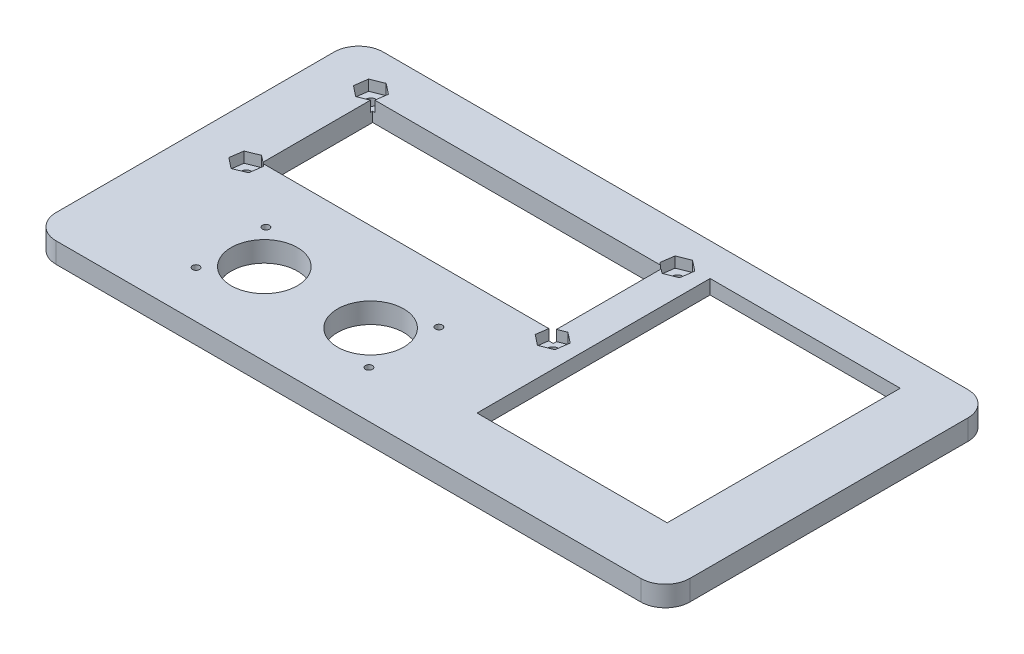
SolidWorks part; units mm, degrees
ref_plane "Front Plane" through (0, 0, 0) normal (0, 0, 1) x (1, 0, 0)
ref_plane "Top Plane" through (0, 0, 0) normal (0, 1, 0) x (1, 0, 0)
ref_plane "Right Plane" through (0, 0, 0) normal (1, 0, 0) x (0, 0, -1)
sketch "Sketch1" plane through (0, 0, 0) normal (0, 1, 0) x (1, 0, 0)
  line L1 (-77.5, -40) -> (77.5, -40)
  line L2 (-77.5, -40) -> (-77.5, 40)
  line L3 (-77.5, 40) -> (77.5, 40)
  line L4 (77.5, -40) -> (77.5, 40)
  line L5 (-77.5, -40) -> (77.5, 40) construction
  line L6 (-77.5, 40) -> (77.5, -40) construction
  point P0 (0, 0)
  dimension "D1" = 155
  dimension "D2" = 80
extrude "Boss-Extrude1" add sketch "Sketch1" along normal blind 5
sketch "Sketch2" plane through (0, 5, 0) normal (0, 1, 0) x (1, 0, 0)
  line L1 (-62.8518, 1.6691) -> (8.446, 1.6691)
  line L2 (-62.8518, 1.6691) -> (-62.8518, 28.7709)
  line L3 (-62.8518, 28.7709) -> (8.446, 28.7709)
  line L4 (8.446, 1.6691) -> (8.446, 28.7709)
  line L5 (-62.8518, 1.6691) -> (8.446, 28.7709) construction
  line L6 (-62.8518, 28.7709) -> (8.446, 1.6691) construction
  line L7 (-67.5, 15.22) -> (12.51, 15.22) construction
  line L8 (-67.5, 33) -> (12.51, 33) construction
  line L9 (-67.5, 33) -> (-67.5, -2.56) construction
  line L10 (-67.5, -2.56) -> (12.51, -2.56) construction
  line L11 (12.51, 33) -> (12.51, -2.56) construction
  line L12 (77.5, 40) -> (-77.5, 40) construction
  line L13 (-77.5, 40) -> (-77.5, -40) construction
  circle A0 centre (-64.96, -0.02) radius 1.27
  circle A1 centre (9.97, -0.02) radius 1.27
  circle A2 centre (9.97, 30.46) radius 1.27
  circle A3 centre (-64.96, 30.46) radius 1.27
  point P0 (-27.2029, 15.22)
  point P6 (-27.2029, 17.22)
  point P20 (-27.495, 15.22)
  dimension "D7" = 2.54
  dimension "D8" = 2.54
  dimension "D1" = 71.2978
  dimension "D2" = 27.1018
  dimension "D3" = 7
  dimension "D4" = 35.56
  dimension "D5" = 80.01
  dimension "D6" = 4.6482
  dimension "D9" = 33.02
  dimension "D10" = 77.47
  dimension "D11" = 5.08
  dimension "D12" = 10
extrude "Screen Cutout" cut sketch "Sketch2" against normal through all
sketch "Sketch8" plane through (0, 5, 0) normal (0, 1, 0) x (1, 0, 0)
  line L1 (-68.0135, 29.2327) -> (-65.4238, 27.202)
  line L2 (-65.4238, 27.202) -> (-62.3704, 28.4293)
  line L3 (-62.3704, 28.4293) -> (-61.9065, 31.6873)
  line L4 (-61.9065, 31.6873) -> (-64.4962, 33.718)
  line L5 (-64.4962, 33.718) -> (-67.5496, 32.4907)
  line L6 (-67.5496, 32.4907) -> (-68.0135, 29.2327)
  line L7 (6.9165, 29.2327) -> (9.5062, 27.202)
  line L8 (9.5062, 27.202) -> (12.5596, 28.4293)
  line L9 (12.5596, 28.4293) -> (13.0235, 31.6873)
  line L10 (13.0235, 31.6873) -> (10.4338, 33.718)
  line L11 (10.4338, 33.718) -> (7.3804, 32.4907)
  line L12 (7.3804, 32.4907) -> (6.9165, 29.2327)
  line L13 (6.9165, -1.2473) -> (9.5062, -3.278)
  line L14 (9.5062, -3.278) -> (12.5596, -2.0507)
  line L15 (12.5596, -2.0507) -> (13.0235, 1.2073)
  line L16 (13.0235, 1.2073) -> (10.4338, 3.238)
  line L17 (10.4338, 3.238) -> (7.3804, 2.0107)
  line L18 (7.3804, 2.0107) -> (6.9165, -1.2473)
  line L19 (-68.0135, -1.2473) -> (-65.4238, -3.278)
  line L20 (-65.4238, -3.278) -> (-62.3704, -2.0507)
  line L21 (-62.3704, -2.0507) -> (-61.9065, 1.2073)
  line L22 (-61.9065, 1.2073) -> (-64.4962, 3.238)
  line L23 (-64.4962, 3.238) -> (-67.5496, 2.0107)
  line L24 (-67.5496, 2.0107) -> (-68.0135, -1.2473)
  circle A0 centre (-64.96, 30.46) radius 2.85 construction
  circle A1 centre (9.97, 30.46) radius 2.85 construction
  circle A2 centre (9.97, -0.02) radius 2.85 construction
  circle A3 centre (-64.96, -0.02) radius 2.85 construction
  dimension "D1" = 5.7
extrude "Screen hex nuts" cut sketch "Sketch8" against normal blind 2.6
sketch "Sketch3" plane through (0, 5, 0) normal (0, 1, 0) x (1, 0, 0)
  line L0 (-40.5818, -20) -> (-14.5818, -20) construction
  line L1 (-48.7318, -11.45) -> (-48.7318, -28.55) construction
  line L2 (-48.7318, -28.55) -> (-6.4318, -28.55) construction
  line L3 (-62.4954, 1.6691) -> (7.3317, 1.6691) construction
  line L4 (-77.5, -40) -> (77.5, -40) construction
  line L7 (-27.5818, 26.9252) -> (-27.5818, -22.8987) construction
  circle A0 centre (-40.5818, -20) radius 8.1
  circle A1 centre (-14.5818, -20) radius 8.1
  circle A2 centre (-48.7318, -11.45) radius 0.85
  circle A3 centre (-6.4318, -11.45) radius 0.85
  circle A4 centre (-6.4318, -28.55) radius 0.85
  circle A5 centre (-48.7318, -28.55) radius 0.85
  point P4 (-27.5818, -28.55)
  point P14 (-27.5818, -20)
  point P19 (-27.5818, 1.6691)
  dimension "D1" = 16.2
  dimension "D2" = 26
  dimension "D3" = 1.7
  dimension "D4" = 17.1
  dimension "D5" = 20
  dimension "D6" = 42.3
  dimension "D7" = 8.55
extrude "Ultrasound Cutouts" cut sketch "Sketch3" against normal through all
sketch "Sketch4" plane through (0, 5, 0) normal (0, 1, 0) x (1, 0, 0)
  circle A0 centre (-21.6513, -28.8183) radius 0.85
  circle A1 centre (20.3487, -11.8183) radius 0.85
  circle A2 centre (-21.6513, -11.8183) radius 0.85
  circle A3 centre (20.3487, -28.8183) radius 0.85
  dimension "D1" = 1.7
  dimension "D2" = 17
  dimension "D3" = 42
extrude "Ultrasound Bolt Holes" [suppressed] cut sketch "Sketch4" against normal through all
sketch "Sketch5" plane through (0, 0, 0) normal (0, -1, 0) x (1, 0, 0)
  line L0 (-6.322, 30.05) -> (-48.622, 30.05) construction
  line L1 (-21.472, 30.05) -> (-33.472, 30.05)
  line L2 (-21.472, 30.05) -> (-21.472, 25.05)
  line L3 (-21.472, 25.05) -> (-33.472, 25.05)
  line L4 (-33.472, 30.05) -> (-33.472, 25.05)
  line L5 (-21.472, 30.05) -> (-33.472, 25.05) construction
  line L6 (-21.472, 25.05) -> (-33.472, 30.05) construction
  circle A0 centre (-6.4318, 28.55) radius 0.85 construction
  point P0 (-27.472, 27.55)
  point P13 (-27.472, 30.05)
  point P14 (-27.472, 30.05)
  dimension "D3" = 1.5
  dimension "D1" = 12
  dimension "D2" = 5
extrude "US Clock cutout" cut sketch "Sketch5" against normal blind 4
sketch "Sketch6" plane through (0, 0, 0) normal (0, -1, 0) x (1, 0, 0)
  line L0 (-21.472, 27.55) -> (-33.472, 27.55) construction
  line L1 (-22.472, 13.3) -> (-32.472, 13.3)
  line L2 (-22.472, 13.3) -> (-22.472, 9.8)
  line L3 (-22.472, 9.8) -> (-32.472, 9.8)
  line L4 (-32.472, 13.3) -> (-32.472, 9.8)
  line L5 (-22.472, 13.3) -> (-32.472, 9.8) construction
  line L6 (-22.472, 9.8) -> (-32.472, 13.3) construction
  line L7 (-21.472, 25.05) -> (-21.472, 30.05) construction
  line L8 (-33.472, 30.05) -> (-33.472, 25.05) construction
  line L9 (-6.5571, 10.6093) -> (-48.8571, 10.6093) construction
  line L10 (-27.472, 5.8213) -> (-27.472, 1.0358) construction
  circle A0 centre (-6.4318, 11.45) radius 0.85 construction
  circle A1 centre (-48.7318, 11.45) radius 0.85 construction
  point P0 (-27.472, 11.55)
  point P20 (-27.472, 27.55)
  dimension "D1" = 10
  dimension "D2" = 3.5
  dimension "D3" = 16
extrude "US Pin cutout" cut sketch "Sketch6" against normal blind 2
fillet "Fillet2" [suppressed] radius 1
ref_plane "Magnet plane" through (0, 0.2, 0) normal (0, -1, 0) x (-1, 0, 0)
sketch "Sketch9" plane through (0, 0.2, 0) normal (0, -1, 0) x (-1, 0, 0)
  line L0 (-77.5, -40) -> (-77.5, 40) construction
  line L1 (-77.5, 40) -> (77.5, 40) construction
  line L2 (77.5, -40) -> (-77.5, -40) construction
  line L3 (77.5, 40) -> (77.5, -40) construction
  circle A0 centre (-71.5, 34) radius 3.15
  circle A1 centre (71.5, 34) radius 3.15
  circle A2 centre (-71.5, -34) radius 3.15
  circle A3 centre (71.5, -34) radius 3.15
  dimension "D1" = 6.3
  dimension "D2" = 6
  dimension "D3" = 6
  dimension "D4" = 6
  dimension "D5" = 6
extrude "Magnet Holes" cut sketch "Sketch9" against normal blind 2.1
fillet "Fillet1" radius 6 4 edges at (77.5, 2.5, -40) (77.5, 2.5, 40) (-77.5, 2.5, 40) (-77.5, 2.5, -40)
sketch "Sketch10" plane through (0, 5, 0) normal (0, 1, 0) x (1, 0, 0)
  line L0 (8.446, 2.439) -> (8.446, 28.0333) construction
  line L1 (16.446, -25) -> (62.946, -25)
  line L2 (16.446, -25) -> (16.446, 32)
  line L3 (16.446, 32) -> (62.946, 32)
  line L4 (62.946, -25) -> (62.946, 32)
  line L5 (16.446, -25) -> (62.946, 32) construction
  line L6 (16.446, 32) -> (62.946, -25) construction
  line L7 (71.5, 40) -> (-71.5, 40) construction
  point P0 (39.696, 3.5)
  dimension "D1" = 46.5
  dimension "D2" = 57
  dimension "D3" = 8
  dimension "D4" = 8
extrude "Keypad cutout" cut sketch "Sketch10" against normal through all
sketch "Sketch11" plane through (0, 0, 0) normal (0, -1, 0) x (1, 0, 0)
  line L0 (58.696, 34.5) -> (58.696, 28.5)
  line L1 (65.696, -35.5) -> (13.696, -35.5)
  line L2 (65.696, -35.5) -> (65.696, 28.5)
  line L3 (65.696, 28.5) -> (13.696, 28.5)
  line L4 (13.696, -35.5) -> (13.696, 28.5)
  line L5 (58.696, 34.5) -> (20.696, 34.5)
  line L6 (58.696, 28.5) -> (20.696, 28.5)
  line L7 (20.696, 34.5) -> (20.696, 28.5)
  line L8 (58.696, 34.5) -> (20.696, 28.5) construction
  line L9 (58.696, 28.5) -> (20.696, 34.5) construction
  line L10 (62.946, -32) -> (16.446, 25) construction
  line L11 (16.446, -32) -> (62.946, 25) construction
  line L12 (39.696, 25.3529) -> (39.696, -31.6471) construction
  line L14 (62.946, -3.5) -> (16.446, -3.5) construction
  point P4 (39.696, 28.5)
  point P5 (39.696, 31.5)
  point P6 (39.696, 28.5)
  point P16 (39.696, -35.5)
  point P23 (65.696, -3.5)
  point P24 (39.696, -3.5)
  line M12 (62.946, 25) -> (62.946, -32)
  line M13 (62.946, -32) -> (16.446, -32)
  line M14 (16.446, -32) -> (16.446, 25)
  line M15 (16.446, 25) -> (62.946, 25)
  dimension "D1" = 52
  dimension "D2" = 64
  dimension "D3" = 38
  dimension "D4" = 6
extrude "Cut-Extrude1" cut sketch "Sketch11" against normal blind 1.5 contours M12 M15 M14 M13 | L4 L1 L2 L3 M15 M12 M13 M14 | L5 L7 L3 L0 region at (39.696, 0, 31.5) region at (62.196, 0, 27.6754) region at (39.696, 0, -3.5)
